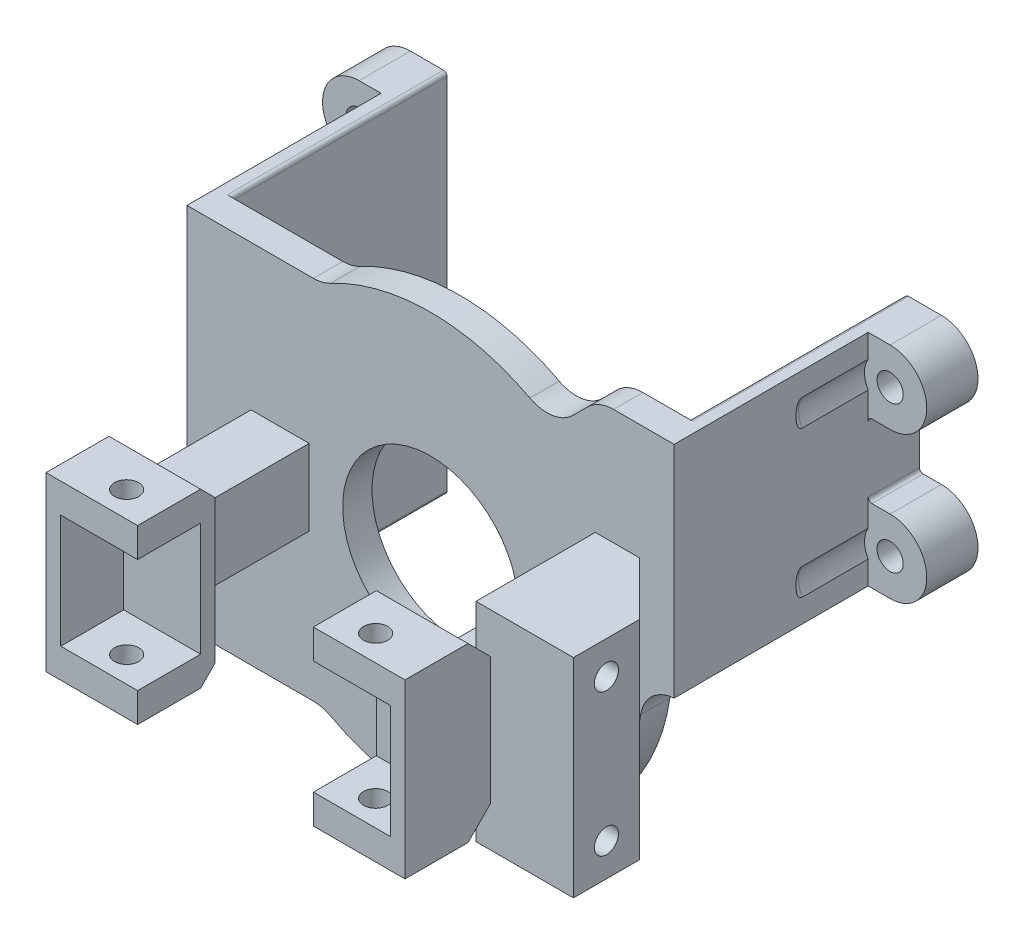
SolidWorks part; units mm, degrees
ref_plane "Front Plane" through (0, 0, 0) normal (0, 0, 1) x (1, 0, 0)
ref_plane "Top Plane" through (0, 0, 0) normal (0, 1, 0) x (1, 0, 0)
ref_plane "Right Plane" through (0, 0, 0) normal (1, 0, 0) x (0, 0, -1)
sketch "Sketch1" plane through (0, 0, 0) normal (0, 0, 1) x (1, 0, 0)
  line L22 (36.25, 10.0017) -> (33.76, 10.0017)
  line L27 (33.26, 19.5) -> (33.26, 10.5017)
  line L33 (-36.25, 15) -> (-33.76, 15)
  line L35 (-36.25, -15) -> (-33.76, -15)
  line L40 (36.25, 20) -> (33.76, 20)
  line L50 (-33.26, -14.5) -> (-33.26, 14.5)
  line L56 (36.25, 0.0017) -> (33.6306, 0.0017)
  line L57 (-36.25, -25) -> (-16, -25)
  line L60 (-36.25, 25) -> (-16, 25)
  line L65 (19.4427, 26.5138) -> (21.4645, 28.5355)
  line L66 (36.25, 30) -> (25, 30)
  circle A3 centre (-36.25, 20) radius 1.79
  circle A4 centre (-36.25, -20) radius 1.79
  arc A7 (-36.25, 25) -> (-36.25, 15) centre (-36.25, 20) ccw
  arc A8 (-36.25, -15) -> (-36.25, -25) centre (-36.25, -20) ccw
  arc A9 (36.25, 20) -> (36.25, 30) centre (36.25, 25) ccw
  arc A23 (33.76, 20) -> (33.26, 19.5) centre (33.76, 19.5) ccw
  arc A28 (-33.76, -15) -> (-33.26, -14.5) centre (-33.76, -14.5) ccw
  arc A29 (-33.76, 15) -> (-33.26, 14.5) centre (-33.76, 14.5) cw
  arc A35 (33.76, 10.0017) -> (33.26, 10.5017) centre (33.76, 10.5017) cw
  circle A36 centre (36.25, 5.0017) radius 1.79
  circle A37 centre (0, 0) radius 12
  circle A53 centre (36.25, 25) radius 1.79
  arc A54 (13.5679, 25.6303) -> (-13.6471, 25.5882) centre (0, 0) ccw
  arc A55 (36.25, 0.0017) -> (36.25, 10.0017) centre (36.25, 5.0017) ccw
  arc A56 (-13.6471, -25.5882) -> (28.6849, -4.2633) centre (0, 0) ccw
  arc A57 (-16, 25) -> (-13.6471, 25.5882) centre (-16, 30) ccw
  arc A58 (-13.6471, -25.5882) -> (-16, -25) centre (-16, -30) ccw
  arc A59 (33.6306, 0.0017) -> (28.6849, -4.2633) centre (33.6306, -4.9983) ccw
  arc A63 (19.4427, 26.5138) -> (13.5679, 25.6303) centre (15.9072, 30.0493) cw
  arc A64 (25, 30) -> (21.4645, 28.5355) centre (25, 25) ccw
extrude "Boss-Extrude1" add sketch "Sketch1" along normal blind 61.5
sketch "Sketch2" plane through (0, 0, 0) normal (0, 0, 1) x (1, 0, 0)
  line L9 (31.25, 30) -> (-31.25, 30)
  line L10 (31.25, 29.5) -> (31.25, 0.5017)
  line L14 (-31.25, -30) -> (31.25, -30)
  line L15 (31.25, -30) -> (31.25, -0.6014)
  line L16 (33.6306, 0.0017) -> (31.75, 0.0017)
  line L55 (31.75, 30) -> (31.25, 30)
  line L59 (-31.25, 25) -> (-31.75, 25)
  line L62 (-31.25, -25) -> (-31.75, -25)
  line L63 (-31.25, 30) -> (-31.25, 25)
  line L64 (-31.25, 24.5) -> (-31.25, -24.5)
  line L65 (-31.25, -25) -> (-31.25, -30)
  arc A13 (31.75, 30) -> (31.25, 29.5) centre (31.75, 29.5) ccw
  arc A18 (31.75, 0.0017) -> (31.25, 0.5017) centre (31.75, 0.5017) cw
  arc A19 (33.6306, 0.0017) -> (31.25, -0.6014) centre (33.6306, -4.9983) ccw
  arc A20 (-31.25, 24.5) -> (-31.75, 25) centre (-31.75, 24.5) ccw
  arc A21 (-31.75, -25) -> (-31.25, -24.5) centre (-31.75, -24.5) ccw
extrude "Cut-Extrude1" cut sketch "Sketch2" along normal blind 29.5
sketch "Sketch3" plane through (0, 0, 61.5) normal (0, 0, 1) x (1, 0, 0)
  line L16 (36.25, 10.0017) -> (33.76, 10.0017)
  line L18 (33.26, 30) -> (36.25, 30)
  line L19 (36.25, 20) -> (33.76, 20)
  line L24 (-33.76, -15) -> (-36.25, -15)
  line L29 (-36.25, 15) -> (-33.76, 15)
  line L30 (-33.26, 14.5) -> (-33.26, 25)
  line L31 (-33.26, -25) -> (-33.26, -14.5)
  line L32 (33.26, 10.5017) -> (33.26, -0.0121)
  line L33 (33.26, 19.5) -> (33.26, 30)
  line L34 (36.25, 0.0017) -> (33.6306, 0.0017)
  line L35 (-36.25, 25) -> (-33.26, 25)
  line L37 (-36.25, -25) -> (-33.26, -25)
  arc A15 (33.26, 10.5017) -> (33.76, 10.0017) centre (33.76, 10.5017) ccw
  arc A18 (36.25, 20) -> (36.25, 30) centre (36.25, 25) ccw
  arc A20 (33.76, 20) -> (33.26, 19.5) centre (33.76, 19.5) ccw
  arc A22 (-36.25, -15) -> (-36.25, -25) centre (-36.25, -20) ccw
  arc A23 (-33.76, -15) -> (-33.26, -14.5) centre (-33.76, -14.5) ccw
  arc A25 (-33.26, 14.5) -> (-33.76, 15) centre (-33.76, 14.5) ccw
  arc A26 (-36.25, 25) -> (-36.25, 15) centre (-36.25, 20) ccw
  arc A28 (36.25, 0.0017) -> (36.25, 10.0017) centre (36.25, 5.0017) ccw
  arc A29 (33.6306, 0.0017) -> (33.26, -0.0121) centre (33.6306, -4.9983) ccw
extrude "Cut-Extrude2" cut sketch "Sketch3" against normal offset from surface (54.5 mm away) 7 up to face at (38.04, 25, 0)
sketch "Sketch4" plane through (0, 0, 61.5) normal (0, 0, 1) x (1, 0, 0)
  line L1 (-12, 11.77) -> (-24.51, 11.77)
  line L2 (-22.5, -7.75) -> (-12, -7.75)
  line L4 (-22.5, 7.75) -> (-12, 7.75)
  line L5 (-12, -11.77) -> (-24.51, -11.77)
  line L6 (12, -11.77) -> (24.51, -11.77)
  line L11 (12, -11.77) -> (12, -7.75)
  line L13 (12, 7.75) -> (12, 11.77)
  line L14 (-22.5, -7.75) -> (-22.5, 7.75)
  line L15 (-12, 7.75) -> (-12, 11.77)
  line L16 (-12, -11.77) -> (-12, -7.75)
  line L24 (12, -7.75) -> (22.5, -7.75)
  line L26 (12, 7.75) -> (22.5, 7.75)
  line L27 (-24.51, -11.77) -> (-24.51, 11.77)
  line L30 (24.51, -11.77) -> (24.51, 11.77)
  line L32 (22.5, -7.75) -> (22.5, 7.75)
  line L35 (24.51, 11.77) -> (12, 11.77)
extrude "Cut-Extrude3" cut sketch "Sketch4" against normal blind 8.6 flip side to cut
sketch "Sketch5" plane through (0, 11.77, 0) normal (0, 1, 0) x (1, 0, 0)
  circle A2 centre (17, -58) radius 1.65
  circle A3 centre (-17, -58) radius 1.65
extrude "Cut-Extrude4" cut sketch "Sketch5" against normal up to surface (23.54 mm away) up to face at (-18.255, -11.77, 57.2)
sketch "Sketch15" plane through (0, 0, 52.9) normal (0, 0, 1) x (1, 0, 0)
  line L1 (-41.25, -29) -> (41.25, -29)
  line L2 (-41.25, -29) -> (-41.25, 30)
  line L3 (-41.25, 30) -> (41.25, 30)
  line L4 (41.25, -29) -> (41.25, 30)
extrude "Cut-Extrude7" cut sketch "Sketch15" against normal offset from surface (19.4 mm away) 4 up to face at (12, 0, 29.5)
sketch "Sketch10" plane through (0, 0, 0) normal (0, 1, 0) x (1, 0, 0)
  line L3 (24.51, -29.5) -> (35.81, -40.8)
  line L5 (35.81, -49.8) -> (35.81, -40.8)
  line L8 (22.5, -49.8) -> (22.5, -29.5)
  line L9 (22.5, -49.8) -> (35.81, -49.8)
  line L10 (22.5, -29.5) -> (24.51, -29.5)
extrude "Boss-Extrude5" add sketch "Sketch10" along normal mid plane 28.42
sketch "Sketch8" plane through (0, 0, 7) normal (0, 0, 1) x (1, 0, 0)
  circle A0 centre (36.25, 5.0017) radius 3.5
  circle A1 centre (36.25, 25) radius 3.5
  circle A2 centre (-36.25, 20) radius 3.5
  circle A3 centre (-36.25, -20) radius 3.5
sketch "Sketch13" plane through (35.81, 0, 0) normal (1, 0, 0) x (0, 0, -1)
  circle A0 centre (-45.3, 9.7) radius 1.65
  circle A1 centre (-45.3, -9.7) radius 1.65
extrude "Cut-Extrude8" cut sketch "Sketch13" against normal up to surface (13.31 mm away) up to face at (22.5, 0, 41.65)
sketch "Sketch16" plane through (22.5, 0, 0) normal (-1, 0, 0) x (0, 0, 1)
  line L1 (48.6486, 9.7) -> (46.9743, 12.6)
  line L2 (46.9743, 12.6) -> (43.6257, 12.6)
  line L3 (43.6257, 12.6) -> (41.9514, 9.7)
  line L4 (41.9514, 9.7) -> (43.6257, 6.8)
  line L5 (43.6257, 6.8) -> (46.9743, 6.8)
  line L6 (46.9743, 6.8) -> (48.6486, 9.7)
  line L7 (48.6486, -9.7) -> (46.9743, -6.8)
  line L8 (46.9743, -6.8) -> (43.6257, -6.8)
  line L9 (43.6257, -6.8) -> (41.9514, -9.7)
  line L10 (41.9514, -9.7) -> (43.6257, -12.6)
  line L11 (43.6257, -12.6) -> (46.9743, -12.6)
  line L12 (46.9743, -12.6) -> (48.6486, -9.7)
extrude "Cut-Extrude9" cut sketch "Sketch16" against normal offset from surface (10.31 mm away) 3 up to face at (35.81, 9.7, 43.65)
sketch "Sketch18" plane through (24.51, 0, 0) normal (1, 0, 0) x (0, 0, -1)
  line L0 (-52.9, 11.77) -> (-46.32, 5.19)
  line L2 (-46.32, 5.19) -> (-33.5, 5.19)
  line L4 (-33.5, 5.19) -> (-33.5, -5.19)
  line L6 (-33.5, -5.19) -> (-46.32, -5.19)
  line L8 (-46.32, -5.19) -> (-52.9, -11.77)
  line L9 (-52.9, -11.77) -> (-52.9, 11.77)
extrude "Boss-Extrude6" add sketch "Sketch18" against normal up to surface (12.51 mm away) up to face at (12, 9.76, 57.2)
extrude "Boss-Extrude7" add sketch "Sketch18<2>" along normal up to surface (-36.51 mm away) from surface up to face at (-12, 9.76, 57.2) starting at face at (-24.51, 0, 57.2)
sketch "Sketch18<2>" plane through (24.51, 0, 0) normal (1, 0, 0) x (0, 0, -1) same geometry as "Sketch18"
sketch "Sketch19" plane through (0, 0, 0) normal (0, 1, 0) x (1, 0, 0)
  line L8 (-16.58, -33.5) -> (16.58, -33.5)
  line L20 (12, -50.9) -> (-12, -50.9)
  line L22 (-12, -50.9) -> (-16.58, -46.32)
  line L24 (-16.58, -46.32) -> (-16.58, -33.5)
  line L26 (12, -50.9) -> (16.58, -46.32)
  line L28 (16.58, -46.32) -> (16.58, -33.5)
extrude "Cut-Extrude10" cut sketch "Sketch19" along normal up to surface (11.77 mm away) from surface up to face at (17, 11.77, 59.65) starting at face at (17, -11.77, 56.35)
extrude "Cut-Extrude11" cut sketch "Sketch8" along normal blind 10
fillet "Fillet2" radius 1 4 edges at (-32.75, -20, 17) (-32.75, 20, 17) (32.75, 25, 17) (32.75, 5.0017, 17)
